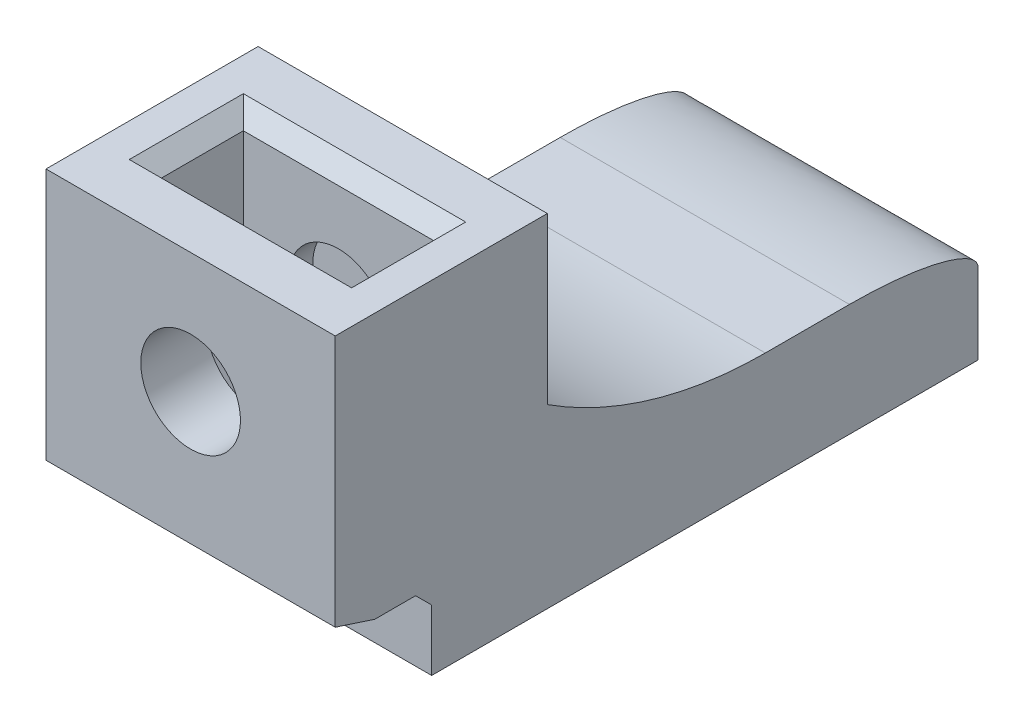
SolidWorks part; units mm, degrees
ref_plane "Front" through (0, 0, 0) normal (0, 0, 1) x (1, 0, 0)
ref_plane "Top" through (0, 0, 0) normal (0, 1, 0) x (1, 0, 0)
ref_plane "Right" through (0, 0, 0) normal (1, 0, 0) x (0, 0, -1)
sketch "Esboço2" plane through (0, 0, 0) normal (1, 0, 0) x (0, 0, -1)
  line L0 (0, 0) -> (0, -16.5)
  line L1 (6, -21.3) -> (40, -21.3)
  line L2 (40, -21.3) -> (40, -14.3)
  line L3 (40, -14.3) -> (26.7647, -14.3)
  line L4 (13.2, -10.3) -> (13.2, 0)
  line L5 (13.2, 0) -> (0, 0)
  line L6 (0, -16.5) -> (6, -16.5)
  line L7 (6, -16.5) -> (6, -21.3)
  arc A0 (26.7647, -14.3) -> (13.2, -10.3) centre (26.7647, 10.7) cw
  spline S0 degree 3 poles (40, -21.3) (40, -19.492) (39.5724, -15.263) (35.5087, -14.3) (34, -14.3) knots 0 0 0 0 0.535357 1 1 1 1
  dimension "D5" = 25
  dimension "D1" = 13.2
  dimension "D3" = 40
  dimension "D4" = 7
  dimension "D6" = 1.5
  dimension "D7" = 1.6
  dimension "D8" = 3.5
  dimension "D9" = 0.4
  dimension "D10" = 6
  dimension "D11" = 4.8
  dimension "D12" = 6
  dimension "D13" = 10.3
  dimension "D14" = 16.5
extrude "Ressalto-extrusão1" add sketch "Esboço2" along normal mid plane 18 contours L1 S0 L3 A0 L4 L5 L0 | S0 L2 L3
chamfer "Chanfro5" distance 1 angle 45 1 edges at (0, -16.5, -6)
chamfer "Chamfer1" distance 0.8 angle 72 1 edges at (0, -16.5, 0) first distance on face at (0, -8.25, 0)
sketch "Esboço3" plane through (0, 0, 0) normal (0, 0, -1) x (-1, 0, 0)
  line L1 (0, -1.7265) -> (0, -7.5) construction
  line L2 (5, -4.6132) -> (0, -1.7265) construction
  line L3 (0, -1.7265) -> (-5, -4.6132) construction
  line L4 (-5, -4.6132) -> (-5, -10.3868) construction
  line L5 (-5, -10.3868) -> (0, -13.2735) construction
  line L6 (0, -13.2735) -> (5, -10.3868) construction
  line L7 (5, -10.3868) -> (5, -4.6132) construction
  circle A0 centre (0, -7.5) radius 3.1
  circle A1 centre (0, -7.5) radius 5 construction
  dimension "D1" = 6.2
  dimension "D2" = 7.5
  dimension "D3" = 10
extrude "Corte-extrusão1" cut sketch "Esboço3" along normal offset from surface (10.7 mm away) 2.5 up to face at (0, -5.15, -13.2)
sketch "Esboço7" plane through (0, 0, -13.2) normal (0, 0, -1) x (-1, 0, 0)
  line L0 (5.9178, -7.5) -> (5.9178, 0)
  line L1 (2.9589, -12.625) -> (5.9178, -7.5)
  line L2 (5.9178, -7.5) -> (2.9589, -2.375)
  line L3 (2.9589, -2.375) -> (-2.9589, -2.375)
  line L4 (-2.9589, -2.375) -> (-5.9178, -7.5)
  line L5 (-5.9178, -7.5) -> (-2.9589, -12.625)
  line L6 (-2.9589, -12.625) -> (2.9589, -12.625)
  line L7 (-9, 0) -> (9, 0) construction
  line L8 (5.9178, 0) -> (-5.9178, 0)
  line L9 (-5.9178, 0) -> (-5.9178, -7.5)
  circle A0 centre (0, -7.5) radius 5.125 construction
  dimension "D1" = 10.25
extrude "Corte-extrusão4" cut sketch "Esboço7" against normal blind 5.1 from offset 4 offset against normal yes
chamfer "Chamfer2" distance 1 angle 45 4 edges at (5.9178, 0, -6.65) (0, 0, -9.2) (-5.9178, 0, -6.65) (0, 0, -4.1)
fillet "Filete1" radius 2 1 edges at (0, -14.3, -40) second distance 8 first distance on face at (0, -17.8, -40)
